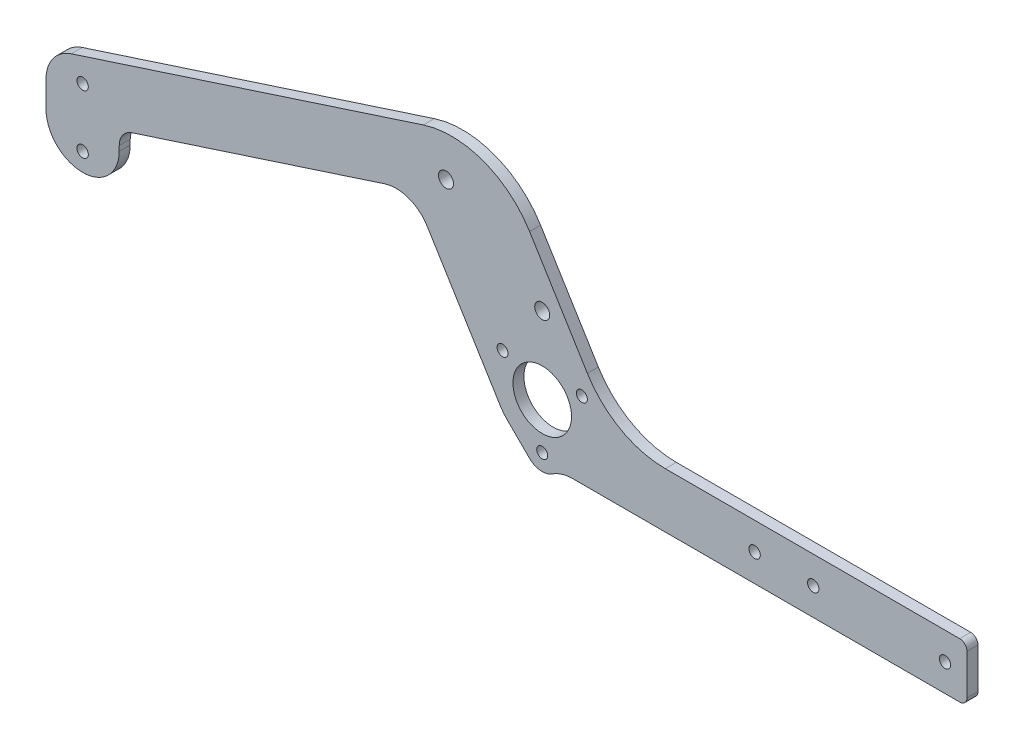
SolidWorks part; units mm, degrees
ref_plane "Спереди" through (0, 0, 0) normal (0, 0, 1) x (1, 0, 0)
ref_plane "Сверху" through (0, 0, 0) normal (0, 1, 0) x (1, 0, 0)
ref_plane "Справа" through (0, 0, 0) normal (1, 0, 0) x (0, 0, -1)
sketch "Эскиз Морковки" plane through (0, 0, 0) normal (0, 0, 1) x (1, 0, 0)
  line L0 (92, -93) -> (92, -7) construction
  line L1 (-53, -93) -> (-53, -7) construction
  line L2 (-198, -7) -> (-164, -7) construction
  line L3 (-198, -93) -> (-53, -93) construction
  line L4 (-198, -7) -> (-216, -7) construction
  line L5 (-53, -93) -> (92, -93) construction
  line L6 (-198, -93) -> (-198, -7) construction
  line L7 (58, -7) -> (92, -7) construction
  line L8 (110, -7) -> (92, -7) construction
  line L9 (-255.5, -93) -> (149.5, -93) construction
  line L10 (-198, -7) -> (-125.5, -7) construction
  line L11 (-125.5, -7) -> (-53, -7) construction
  line L12 (-125.5, -7) -> (0, 0) construction
  line L13 (0, 0) -> (92, -7) construction
  line L14 (-125.5, -7) -> (-125.5, 12) construction
  circle A0 centre (-198, -93) radius 57.5 construction
  circle A1 centre (-53, -93) radius 57.5 construction
  circle A2 centre (92, -93) radius 57.5 construction
  circle A3 centre (-216, -7) radius 1.55 construction
  circle A4 centre (-164, -7) radius 1.55 construction
  circle A5 centre (58, -7) radius 1.55 construction
  circle A6 centre (110, -7) radius 1.55 construction
  circle A7 centre (-87, -7) radius 1.55 construction
  circle A8 centre (-35, -7) radius 1.55 construction
  circle A9 centre (-125.5, 12) radius 1.55
  circle A10 centre (-125.5, -4) radius 1.55
  circle A11 centre (-125.5, -19) radius 2.05
  circle A12 centre (0, 21) radius 2.05
  circle A13 centre (-180, -7) radius 1.55
  circle A14 centre (74, -7) radius 1.55
  circle A15 centre (-71, -7) radius 1.55
  point P31 (-181, -7)
  point P42 (3.6612, 21.6932)
  point P43 (-125.5, -93)
  point P44 (0, 0)
  point P45 (0, -16.093)
  point P46 (0, 23.0194)
  dimension "D1" = 115
  dimension "D4" = 3.1
  dimension "D7" = 34
  dimension "D11" = 4.1
  dimension "D19" = 18
  dimension "D20" = 18
  dimension "D21" = 18
  dimension "D2" = 145
  dimension "D3" = 86
  dimension "D5" = 18
  dimension "D6" = 34
  dimension "D8" = 21
  dimension "D9" = 145
  dimension "D10" = 53
  dimension "D13" = 16
  dimension "D14" = 12
  dimension "D15" = 7
  dimension "D16" = 15
  dimension "D22" = 18
sketch "эскиз 1" plane through (0, 0, 0) normal (0, 0, 1) x (1, 0, 0)
  line L0 (-222, 0.5) -> (-222, -14.5)
  line L1 (-222, -14.5) -> (-152, -14.5)
  line L2 (-152, -14.5) -> (-152, -30)
  line L3 (-222, 0.5) -> (-141.7325, 0.5)
  line L4 (-53, -93) -> (92, -93) construction
  line L5 (-29, -14.5) -> (-29, 0.5)
  line L6 (-152, -30) -> (-99, -30)
  line L9 (-131.745, -10) -> (-119.255, -10)
  line L10 (-99, -14.5) -> (-99, -30)
  line L11 (-53, 0.5) -> (-53, -93) construction
  line L12 (-99, -14.5) -> (-29, -14.5)
  line L13 (-29, -14.5) -> (-99, -14.5)
  line L14 (-135.5, -9) -> (-115.5, -9) construction
  line L15 (-109.2675, 0.5) -> (-29, 0.5)
  line L16 (-125.5, -7) -> (-125.5, 12) construction
  line L17 (-53, -93) -> (-53, -7) construction
  line L18 (-198, 0.5) -> (-198, -14.5) construction
  line L19 (-198, -93) -> (-198, -7) construction
  line L21 (-125.5, -10) -> (-125.5, -30) construction
  line L22 (-135.5, -10) -> (-135.5, 1) construction
  line L23 (-115.5, -9.2682) -> (-115.5, 1) construction
  line L24 (-141.7325, 0.5) -> (-141.7325, -10) construction
  line L25 (-141.7325, -10) -> (-109.2675, -10) construction
  line L26 (-109.2675, -10) -> (-109.2675, 0.5) construction
  circle A0 centre (-216, -7) radius 1.55
  circle A1 centre (-164, -7) radius 1.55
  circle A2 centre (-125.5, -19) radius 2.05
  circle A3 centre (-87, -7) radius 1.55
  circle A4 centre (-35, -7) radius 1.55
  circle A5 centre (-35, -7) radius 1.55 construction
  circle A6 centre (-87, -7) radius 1.55 construction
  circle A7 centre (-125.5, -19) radius 2.05 construction
  circle A8 centre (-164, -7) radius 1.55 construction
  circle A9 centre (-216, -7) radius 1.55 construction
  circle A10 centre (-125.5, 1) radius 10 construction
  circle A11 centre (-125.5, -19) radius 20 construction
  arc A12 (-119.255, -10) -> (-109.2675, 0.5) centre (-119.255, 0) ccw
  arc A13 (-131.745, -10) -> (-141.7325, 0.5) centre (-131.745, 0) cw
  circle A14 centre (-180, -7) radius 1.55
  circle A15 centre (-180, -7) radius 1.55 construction
  circle A16 centre (-71, -7) radius 1.55
  circle A17 centre (-71, -7) radius 1.55 construction
  point P25 (-125.5, -30)
  point P33 (-222, -7)
  dimension "D6" = 9
  dimension "D5" = 20
  dimension "D1" = 24
  dimension "D2" = 24
  dimension "D3" = 15
  dimension "D4" = 11
  dimension "D7" = 70
  dimension "D9" = 5
extrude "тело маленькой арки" [suppressed] add sketch "эскиз 1" along normal blind 3
fillet "Скругление2" [suppressed] radius 6
fillet "Скругление3" [suppressed] radius 20
fillet "Скругление16" [suppressed] radius 8
fillet "Скругление18" [suppressed] radius 2
sketch "Эскиз1" plane through (0, 0, 0) normal (0, 0, 1) x (1, 0, 0)
  line L0 (3.3551, 27) -> (19.6412, 0.5)
  line L1 (19.6412, 0.5) -> (116, 0.5)
  line L2 (116, 0.5) -> (116, -14.5)
  line L3 (116, -14.5) -> (4.4892, -14.5)
  line L4 (-3.3551, 27) -> (-15.9904, 54.0965) construction
  line L5 (-15.1594, 4.4916) -> (-11.5016, -7.0685) construction
  line L6 (-11.5016, -7.0685) -> (-35.5025, 31.9847)
  line L8 (-128.5902, 17.5106) -> (-15.9904, 54.0965)
  line L9 (-135.5, 1) -> (-135.5, 8)
  line L10 (52, 0.5) -> (52, -14.5) construction
  line L11 (-115.5, 5.9919) -> (-35.5025, 31.9847)
  line L12 (-11.6948, 10.8274) -> (-3.5167, 13.0339) construction
  line L13 (92, -93) -> (92, -7) construction
  line L14 (3.6898, -15.3742) -> (4.4892, -14.5)
  line L15 (-3.5294, -15.5417) -> (-9.5294, -9.5625)
  line L16 (-135.5, -9) -> (-115.5, -9) construction
  line L17 (-115.5, 1) -> (-115.5, 5.9919)
  line L18 (-125.5, 12) -> (-125.5, -9) construction
  line L19 (-125.5, -7) -> (-125.5, 12) construction
  line L20 (11.4696, 10.8826) -> (6.0147, 12.0861) construction
  line L21 (-115.5, -9) -> (-115.5, 1) construction
  line L22 (3.3551, 27) -> (-3.3551, 27) construction
  line L23 (-135.5, 18) -> (-115.5, 18) construction
  line L24 (3.3551, 27) -> (-13.7458, 54.8258)
  line L25 (-13.7458, 54.8258) -> (-15.9904, 54.0965)
  line L27 (15.2242, 4.7143) -> (13.046, -3.4714) construction
  line L31 (-135.5, 1) -> (-135.5, -9) construction
  line L32 (-15.2337, 4.7266) -> (-12.6829, -3.3351) [skipped]
  circle A0 centre (-125.5, -4) radius 1.55
  circle A1 centre (-125.5, 12) radius 1.55
  circle A2 centre (-125.5, 12) radius 1.55 construction
  circle A3 centre (-125.5, -4) radius 1.55 construction
  circle A4 centre (0, 0) radius 8
  circle A5 centre (0, 0) radius 13.5 construction
  arc A6 (-11.6948, 10.8274) -> (-15.1594, 4.4916) centre (-10.3923, 6) ccw construction
  circle A7 centre (0, 21) radius 6 construction
  arc A8 (-3.5294, -15.5417) -> (3.6898, -15.3742) centre (0, -12) ccw
  arc A9 (15.2242, 4.7143) -> (11.4696, 10.8826) centre (10.3923, 6) ccw construction
  arc A11 (-9.5294, -9.5625) -> (-11.5016, -7.0685) centre (0, 0) cw
  circle A12 centre (0, 0) radius 12 construction
  circle A13 centre (0, -12.5) radius 1.5
  circle A14 centre (-10.8253, 6.25) radius 1.5
  circle A15 centre (10.8253, 6.25) radius 1.5
  circle A17 centre (110, -7) radius 1.55
  circle A18 centre (58, -7) radius 1.55
  circle A19 centre (58, -7) radius 1.55 construction
  circle A20 centre (110, -7) radius 1.55 construction
  circle A21 centre (0, 21) radius 2.05
  circle A22 centre (0, 21) radius 2.05 construction
  arc A23 (-135.5, 1) -> (-115.5, 1) centre (-125.5, 1) ccw
  arc A24 (-128.5902, 17.5106) -> (-135.5, 8) centre (-125.5, 8) ccw
  circle A26 centre (74, -7) radius 1.55
  circle A27 centre (74, -7) radius 1.55 construction
  circle A28 centre (0, 0) radius 12.5 construction
  point P27 (116, -7)
  point P33 (0, 27)
  point P62 (0, 0)
  point P68 (0, 0)
  dimension "D2" = 16
  dimension "D3" = 3
  dimension "D5" = 5
  dimension "D6" = 24
  dimension "D7" = 27
  dimension "D14" = 3
  dimension "D17" = 12
  dimension "D18" = 6
  dimension "D13" = 6
  dimension "D22" = 20
  dimension "D4" = 18
  dimension "D9" = 6
  dimension "D19" = 25
  dimension "D1" = 15
  dimension "D8" = 10
  dimension "D10" = 24
  dimension "D12" = 15
  dimension "D15" = 3
  dimension "D21" = 5
extrude "тело большой арки" add sketch "Эскиз1" along normal mid plane 3
fillet "Скругление7" [suppressed] radius 15
fillet "Скругление8" [suppressed] radius 40
fillet "Скругление17" [suppressed] radius 8
fillet "Скругление23" [suppressed] radius 2
fillet "Скругление25" [suppressed] radius 25
fillet "Скругление26" radius 25 1 edges at (-13.7458, 54.8258, 0)
fillet "Скругление27" radius 10 1 edges at (-35.5025, 31.9847, 0)
fillet "Скругление29" radius 25 1 edges at (19.6412, 0.5, 0)
fillet "Скругление30" radius 10 1 edges at (4.4892, -14.5, 0)
fillet "Скругление31" [suppressed] radius 5
fillet "Скругление32" radius 5 1 edges at (-115.5, 5.9919, 0)
sketch "Эскиз2" plane through (0, 0, -1.5) normal (0, 0, -1) x (-1, 0, 0)
  line L8 (36.4448, 29.4254) -> (16.1016, 48.4275) construction
  circle A0 centre (26.2732, 38.9264) radius 2.05
  arc A2 (42.9901, 29.5518) -> (31.3803, 25.2772) centre (39.8999, 20.0412) ccw construction
  arc A4 (32.4648, 48.7436) -> (3.4402, 38.057) centre (24.7394, 24.9672) ccw construction
  circle A5 centre (0, 21) radius 2.05 construction
  point P2 (26.2732, 38.9264)
extrude "Под_ребро_жесткости" cut sketch "Эскиз2" against normal through all
fillet "Скругление33" radius 2 2 edges at (116, -14.5, 0) (116, 0.5, 0)
